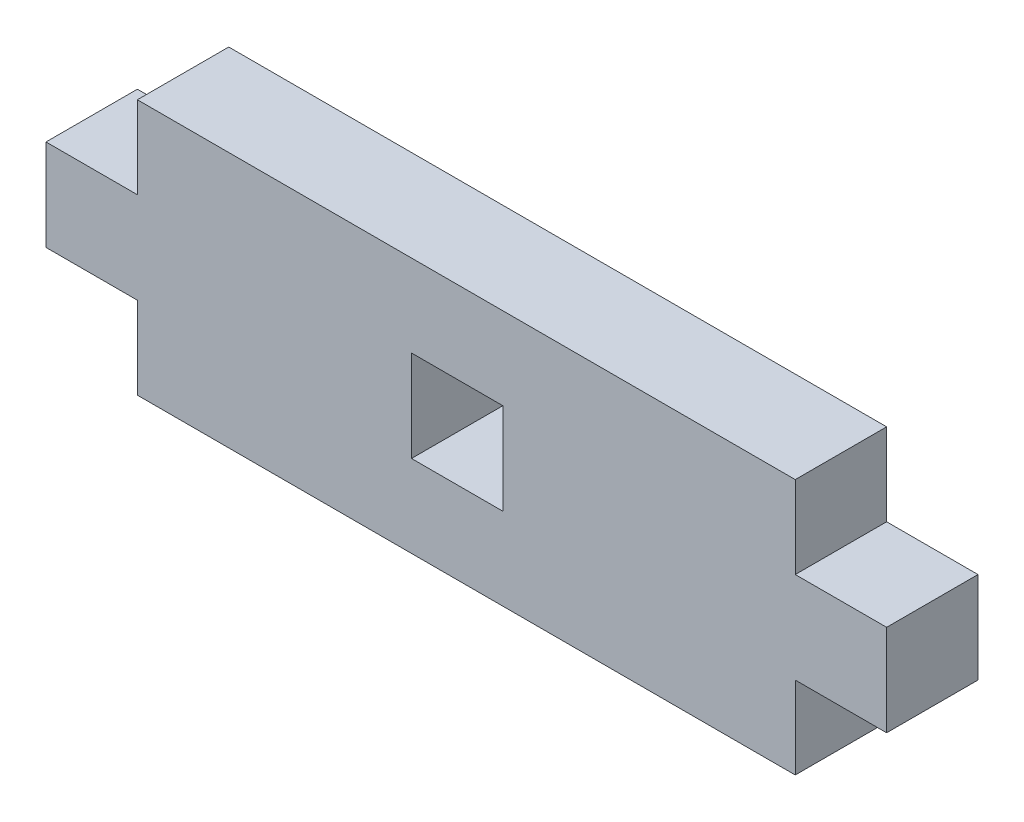
SolidWorks part; units mm, degrees
ref_plane "Front Plane" through (0, 0, 0) normal (0, 0, 1) x (1, 0, 0)
ref_plane "Top Plane" through (0, 0, 0) normal (0, 1, 0) x (1, 0, 0)
ref_plane "Right Plane" through (0, 0, 0) normal (1, 0, 0) x (0, 0, -1)
sketch "Sketch2" plane through (0, 0, 0) normal (0, 0, 1) x (1, 0, 0)
  line L0 (0, 4.5) -> (0, 9.5)
  line L1 (0, -2.75) -> (0, 2.75) construction
  line L2 (0, 9.5) -> (5, 9.5)
  line L3 (5, 9.5) -> (5, 14)
  line L4 (2.75, 0) -> (-2.75, 0) construction
  line L5 (5, 0) -> (41, 0)
  line L6 (41, 9.5) -> (41, 14)
  line L7 (41, 9.5) -> (46, 9.5)
  line L8 (46, 9.5) -> (46, 4.5)
  line L9 (46, 4.5) -> (41, 4.5)
  line L10 (41, 0) -> (41, 4.5)
  line L11 (41, 14) -> (5, 14)
  line L12 (5, 0) -> (5, 4.5)
  line L13 (5, 4.5) -> (0, 4.5)
  dimension "D1" = 36
  dimension "D2" = 5
  dimension "D3" = 14
  dimension "D4" = 5
extrude "Boss-Extrude1" add sketch "Sketch2" along normal blind 5
sketch "Sketch3" plane through (0, 0, 5) normal (0, 0, 1) x (1, 0, 0)
  line L0 (41, 0) -> (41, 4.5) construction
  line L1 (41, 14) -> (5, 14) construction
  line L2 (20, 9.5) -> (20, 4.5)
  line L4 (25, 4.5) -> (20, 4.5)
  line L9 (25, 9.5) -> (25, 4.5)
  line L10 (25, 9.5) -> (20, 9.5)
  line L12 (23, 14) -> (23, -3.9207) construction
  dimension "D1" = 16
extrude "Cut-Extrude1" cut sketch "Sketch3" against normal through all
